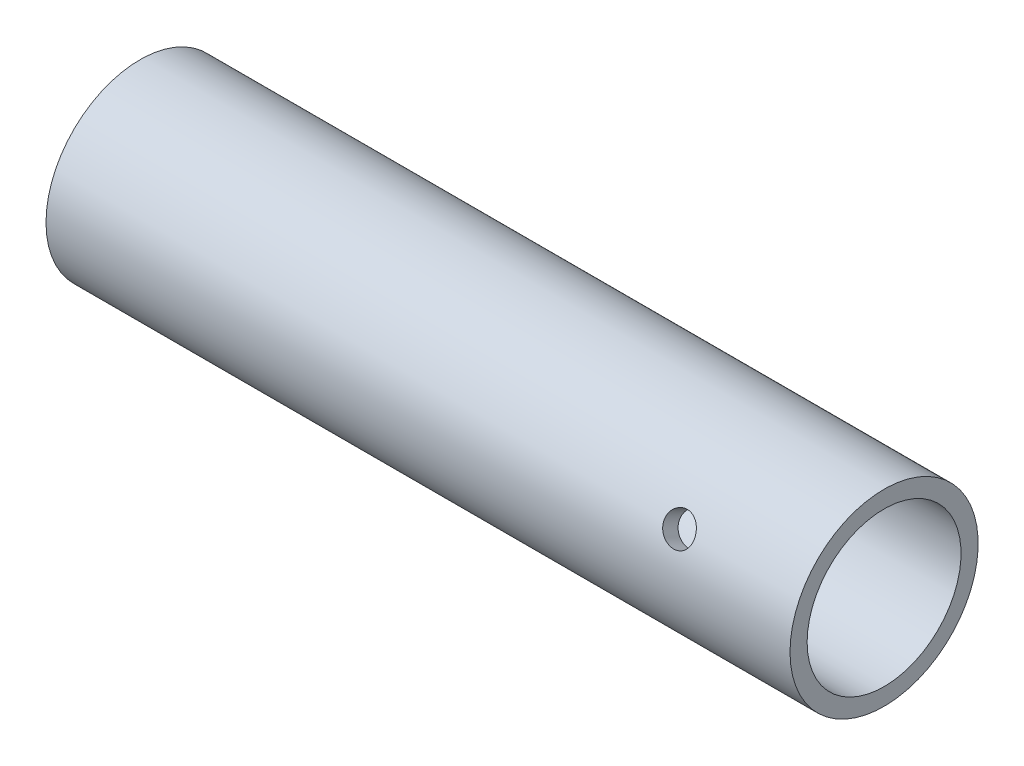
SolidWorks part; units mm, degrees
ref_plane "Front Plane" through (0, 0, 0) normal (0, 0, 1) x (1, 0, 0)
ref_plane "Top Plane" through (0, 0, 0) normal (0, 1, 0) x (1, 0, 0)
ref_plane "Right Plane" through (0, 0, 0) normal (1, 0, 0) x (0, 0, -1)
sketch "Sketch3" plane through (0, 0, 0) normal (0, 0, 1) x (1, 0, 0)
  line L0 (-58.5481, 189.9573) -> (284.033, 189.9573) construction
  line L2 (213.4012, -189.6279) -> (558.7345, -189.6279) construction
  line L4 (263.0584, -148.5737) -> (308.4812, -148.5737) construction
  line L42 (295.0584, -144.0737) -> (305.0584, -144.0737)
  line L43 (305.0584, -144.0737) -> (305.0584, -143.0737)
  line L45 (261.5584, -143.0737) -> (305.0584, -143.0737)
  line L55 (261.5584, -144.3237) -> (261.5584, -148.0737)
  line L63 (263.0584, -148.0737) -> (263.0584, -144.5737)
  line L64 (263.0584, -148.0737) -> (261.5584, -148.0737)
  line L65 (263.0584, -144.5737) -> (295.0584, -144.5737)
  line L66 (295.0584, -144.5737) -> (295.0584, -144.0737)
  line L97 (261.5584, -144.3237) -> (261.5584, -143.0737)
  dimension "D2" = 1.5
  dimension "D3" = 1
  dimension "D4" = 1
  dimension "D5" = 4
  dimension "D6" = 4.5
  dimension "D7" = 10
  dimension "D10" = 43.5
revolve "Revolve19" add sketch "Sketch3" angle 360 about L4 region at (280.3466, -143.9859, 0)
ref_plane "Plane1" through (0, -26.4476, -53.8513) normal (0, 0.4408, 0.8976) x (1, 0, 0)
sketch "Sketch4" plane through (0, -26.4476, -53.8513) normal (0, 0.4408, 0.8976) x (1, 0, 0)
  circle A0 centre (298.0243, -133.3586) radius 0.9
  dimension "D1" = 1.8
extrude "Cut-Extrude1" cut sketch "Sketch4" against normal through all
ref_axis "Axis1" through (298.0243, -146.9731, 3.2591) along (0, 0.4408, 0.8976)
ref_plane "Plane8" through (0, -31.2967, -63.7249) normal (0, -0.4408, -0.8976) x (-1, 0, 0)
